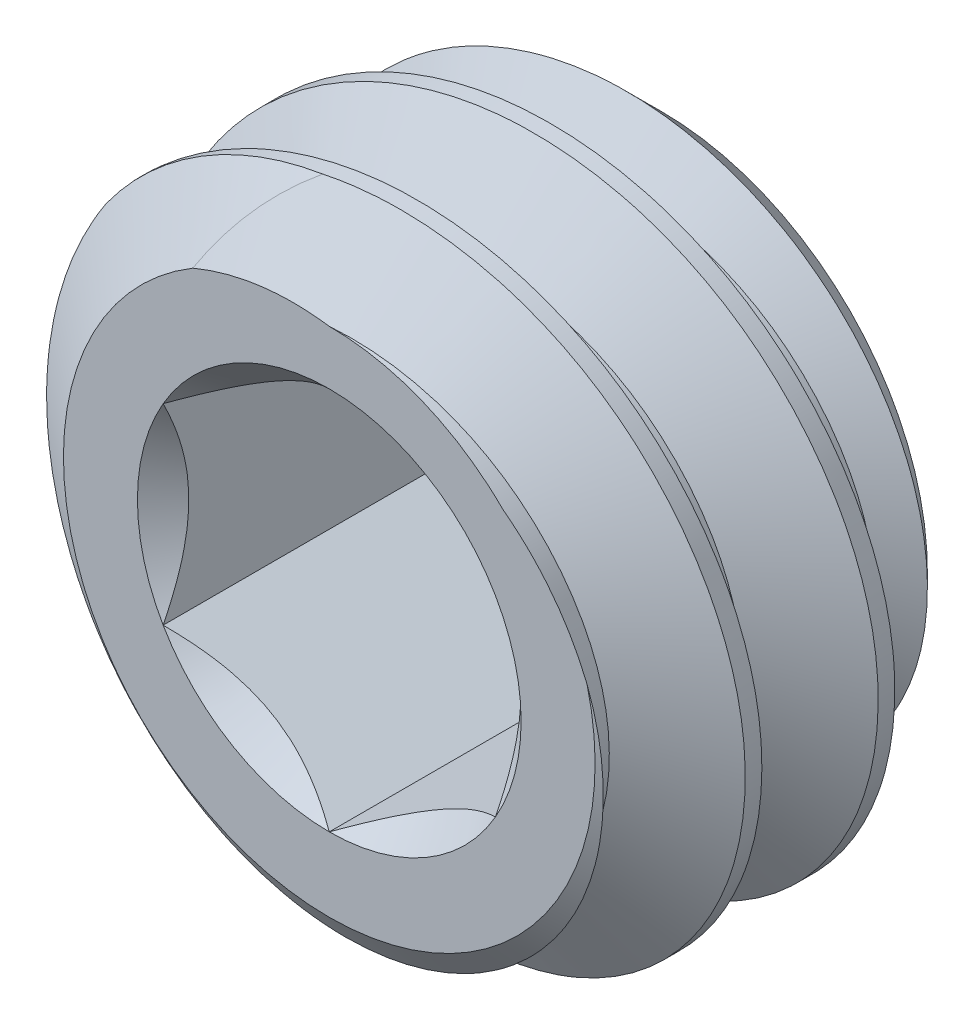
SolidWorks part; units mm, degrees
ref_plane "Front" through (0, 0, 0) normal (0, 0, 1) x (1, 0, 0)
ref_plane "Top" through (0, 0, 0) normal (0, 1, 0) x (1, 0, 0)
ref_plane "Right" through (0, 0, 0) normal (1, 0, 0) x (0, 0, -1)
sketch "Sketch22" plane through (0, 0, 0) normal (1, 0, 0) x (0, 0, -1)
  line L0 (-1.5875, 0) -> (-1.5875, 2.54)
  line L1 (-1.5875, 2.54) -> (-1.1429, 3.175)
  line L2 (-1.1429, 3.175) -> (0.9525, 3.175)
  line L3 (0.9525, 3.175) -> (1.5875, 2.54)
  line L5 (0, 0) -> (-1.5875, 0)
  line L6 (0, 0) -> (1.5875, 0) construction
  line L7 (1.5875, 0) -> (1.5875, 2.54) construction
  line L9 (-1.1429, -3.175) -> (0.9525, -3.175) construction
  line L10 (1.5875, 2.54) -> (1.5875, 0)
  line L11 (1.5875, 0) -> (0, 0)
  dimension "Dia" = 6.35
  dimension "Length" = 3.175
  dimension "D3" = 35
  dimension "D6" = 45
  dimension "D7" = 5.08
revolve "Revolve1" add sketch "Sketch22" angle 360 about L6
ref_plane "Plane1" through (0, 0, -1.5875) normal (0, 0, 1) x (1, 0, 0)
sketch "Sketch27" plane through (0, 0, -1.5875) normal (0, 0, 1) x (1, 0, 0)
  circle A0 centre (0, 0) radius 3.175 construction
  circle A1 centre (0, 0) radius 3.175
curve "Helix/Spiral1" pitch 1.27 height 4.445 radius 3.175 centre (0, 0, -1.5875) axis (0, 0, 1) start towards (0, 1, 0)
sketch "Sketch28" plane through (0, 0, 0) normal (1, 0, 0) x (0, 0, -1)
  line L0 (1.5875, 3.175) -> (2.6988, 3.175)
  line L1 (2.6988, 3.175) -> (2.2225, 2.3501)
  line L2 (2.2225, 2.3501) -> (2.0637, 2.3501)
  line L3 (2.0637, 2.3501) -> (1.5875, 3.175)
  line L4 (1.8256, 2.7626) -> (2.4606, 2.7626) construction
  line L6 (-1.1429, 3.175) -> (0.9525, 3.175) construction
  line L7 (1.5875, 6.1049) -> (1.5875, -6.1049) construction
  dimension "D1" = 0.1588
  dimension "D3" = 60
  dimension "D2" = 0.635
sweep "Cut-Sweep2" cut profiles "Sketch28" path "Helix/Spiral1" align with end faces yes
sketch "Sketch23" plane through (0, 0, 1.5875) normal (0, 0, 1) x (1, 0, 0)
  line L1 (0, 1.8331) -> (-1.5875, 0.9165)
  line L2 (-1.5875, 0.9165) -> (-1.5875, -0.9165)
  line L3 (-1.5875, -0.9165) -> (0, -1.8331)
  line L4 (0, -1.8331) -> (1.5875, -0.9165)
  line L5 (1.5875, -0.9165) -> (1.5875, 0.9165)
  line L6 (1.5875, 0.9165) -> (0, 1.8331)
  circle A0 centre (0, 0) radius 1.5875 construction
  dimension "Hex" = 3.175
extrude "Cut-Extrude10" cut sketch "Sketch23" against normal through all
sketch "Sketch24" plane through (0, 0, 1.5875) normal (0, 0, 1) x (1, 0, 0)
  circle A0 centre (0, 0) radius 1.8331
extrude "Cut-Extrude11" cut sketch "Sketch24" against normal through all draft 45
sketch "Sketch30" plane through (0, 0, 0) normal (1, 0, 0) x (0, 0, -1)
  line L0 (-1.1429, 3.175) -> (0.9525, 3.175) construction
  line L1 (-1.5875, 0) -> (-1.5875, 2.54) construction
  line L2 (1.5875, 0) -> (1.5875, 2.54) construction
  line L3 (-1.1429, -3.175) -> (0.9525, -3.175) construction
  point P0 (-1.5875, 3.175)
  point P1 (1.5875, 3.175)
  point P2 (1.5875, -3.175)
  point P11 (0, -3.175)
equation "\"D7@Sketch22\"=\"Dia@Sketch22\"*.8"
equation "\"D1@Sketch28\" = \"D4@Helix/Spiral1\" * .125"
equation "\"D3@Helix/Spiral1\" = \"Length@Sketch22\" + \"D4@Helix/Spiral1\""
equation "\"D2@Sketch28\" = \"D4@Helix/Spiral1\" * .5"
